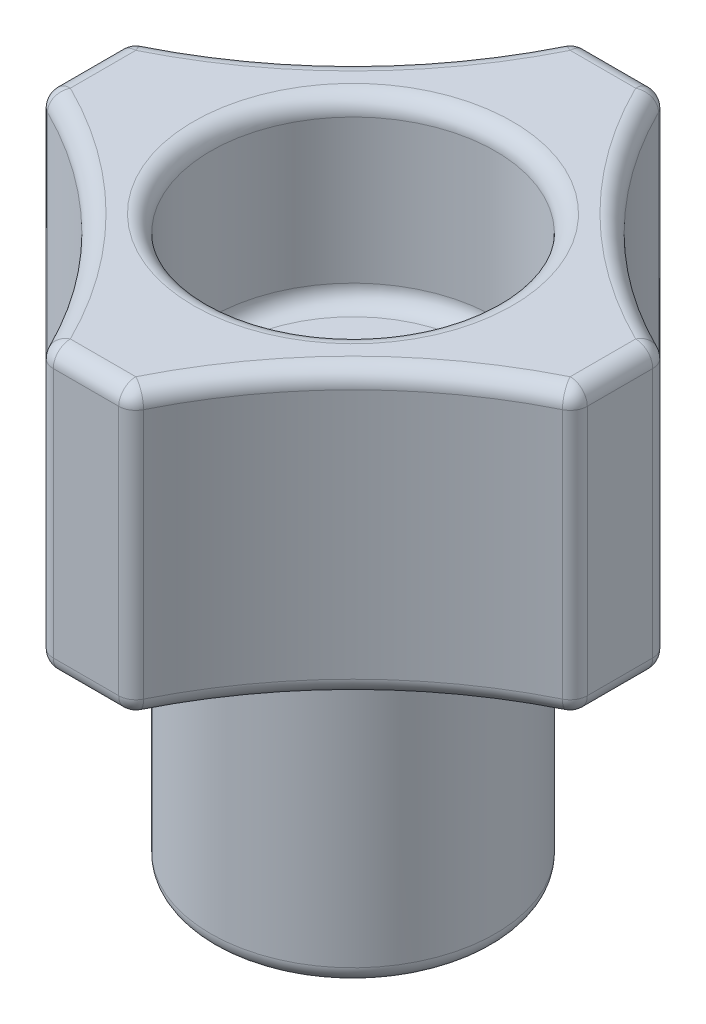
SolidWorks part; units mm, degrees
ref_plane "Front" through (0, 0, 0) normal (0, 0, 1) x (1, 0, 0)
ref_plane "Top" through (0, 0, 0) normal (0, 1, 0) x (1, 0, 0)
ref_plane "Right" through (0, 0, 0) normal (1, 0, 0) x (0, 0, -1)
sketch "Sketch1" plane through (0, 0, 0) normal (0, 1, 0) x (1, 0, 0)
  line L1 (-11.9063, 11.9063) -> (11.9062, 11.9063)
  line L2 (-11.9063, 11.9063) -> (-11.9063, -11.9062)
  line L3 (-11.9063, -11.9062) -> (11.9062, -11.9062)
  line L4 (11.9062, 11.9063) -> (11.9062, -11.9062)
  line L5 (-11.9063, 11.9063) -> (11.9062, -11.9062) construction
  line L6 (-11.9063, -11.9062) -> (11.9062, 11.9063) construction
  point P0 (0, 0)
  dimension "D1" = 23.8125
extrude "Boss-Extrude1" add sketch "Sketch1" along normal blind 12.7
sketch "Sketch3" plane through (0, 12.7, 0) normal (0, 1, 0) x (1, 0, 0)
  line L0 (0, 0) -> (0, 50.8) construction
  line L1 (0, 0) -> (50.8, 0) construction
  circle A0 centre (20.6375, 20.6375) radius 20.6375
  dimension "D2" = 41.275
  dimension "D1" = 50.8
extrude "Cut-Extrude1" cut sketch "Sketch3" against normal through all
ref_axis "Axis1" through (0, 50, 0) along (0, -1, 0)
pattern_circular "CirPattern1" count 4 over 360 about axis through (0, 50, 0) along (0, -1, 0) of "Cut-Extrude1"
sketch "Sketch4" plane through (0, 0, 0) normal (0, -1, 0) x (1, 0, 0)
  circle A0 centre (0, 0) radius 6.35
  dimension "D1" = 12.7
extrude "Boss-Extrude2" add sketch "Sketch4" along normal blind 12.7
sketch "Sketch5" plane through (0, 12.7, 0) normal (0, 1, 0) x (1, 0, 0)
  circle A0 centre (0, 0) radius 3.175
  dimension "D1" = 6.35
extrude "Cut-Extrude2" cut sketch "Sketch5" against normal through all
sketch "Sketch6" plane through (0, 12.7, 0) normal (0, 1, 0) x (1, 0, 0)
  circle A0 centre (0, 0) radius 6.35
  dimension "D1" = 12.7
extrude "Cut-Extrude3" cut sketch "Sketch6" against normal blind 7.9375
fillet "Fillet1" radius 0.762 30 edges at (0, 0, 6.35) (0, 12.7, 11.9062) (-11.9063, 12.7, 0) (0, 12.7, -11.9063) (11.9062, 12.7, 0) (0, 0, 11.9062) (-11.9063, 0, 0) (0, 0, -11.9063) (11.9062, 0, 0) (11.9062, 6.35, -1.938) (1.938, 6.35, -11.9063) (6.0446, 0, -6.0446) (6.0446, 12.7, -6.0446) (11.9062, 6.35, 1.938) (1.938, 6.35, 11.9062) (6.0446, 0, 6.0446) (6.0446, 12.7, 6.0446) (-11.9063, 6.35, 1.938) (-1.938, 6.35, 11.9062) (-6.0446, 12.7, 6.0446) (-6.0446, 0, 6.0446) (-1.938, 6.35, -11.9063) (-11.9063, 6.35, -1.938) (-6.0446, 12.7, -6.0446) (-6.0446, 0, -6.0446) (0, -12.7, -6.35) (0, -12.7, 3.175) (0, 4.7625, 3.175) (0, 4.7625, 6.35) (0, 12.7, 6.35)
